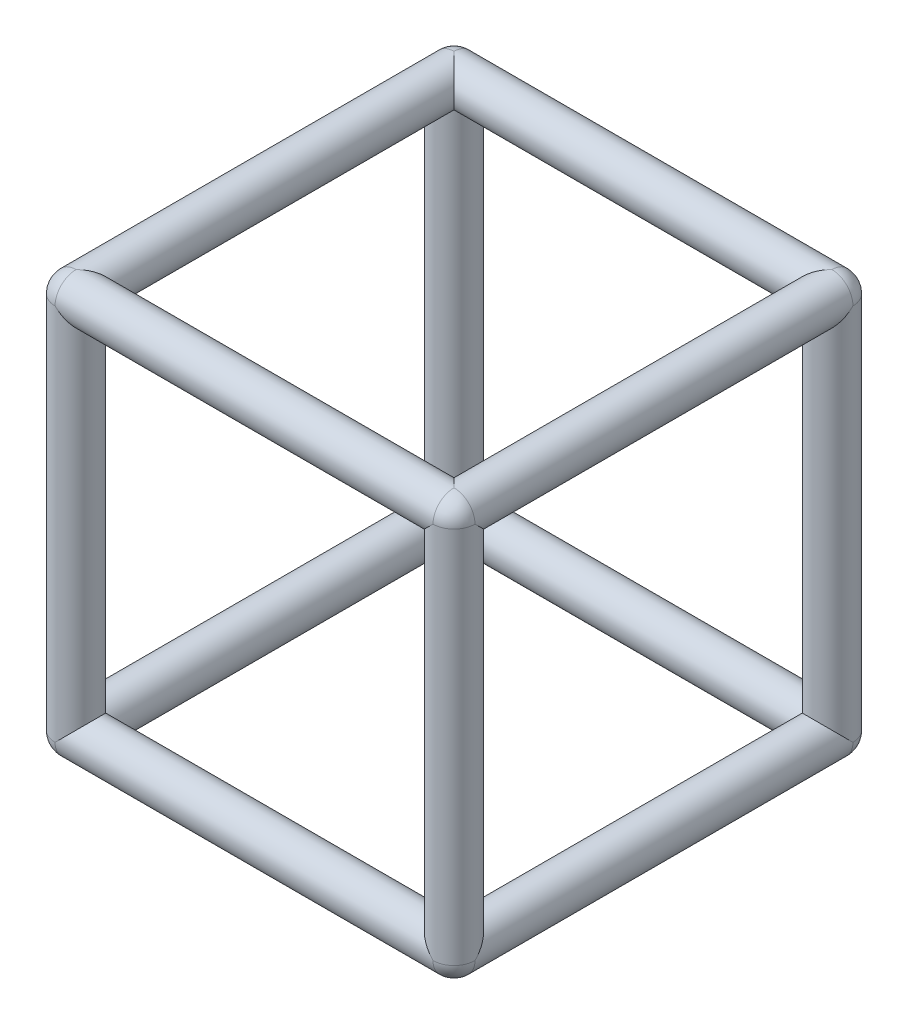
SolidWorks part; units mm, degrees
ref_plane "Front Plane" through (0, 0, 0) normal (0, 0, 1) x (1, 0, 0)
ref_plane "Top Plane" through (0, 0, 0) normal (0, 1, 0) x (1, 0, 0)
ref_plane "Right Plane" through (0, 0, 0) normal (1, 0, 0) x (0, 0, -1)
other "Bounding Box"
ref_plane "Default Plane" through (-139.7, 0, 139.7) normal (0, 0, -1) x (-1, 0, 0)
sketch "Sketch5" plane through (0, 0, 0) normal (0, 1, 0) x (1, 0, 0)
  line L0 (-114.3, 114.3) -> (-63.6437, 114.3) construction
  line L1 (-114.3, 114.3) -> (-114.3, 62.9666) construction
  circle A0 centre (-114.3, 114.3) radius 12.7
  dimension "D1" = 25.4
  dimension "D2" = 114.3
  dimension "D3" = 114.3
extrude "Boss-Extrude2" add sketch "Sketch5" along normal blind 254
fillet "Fillet2" radius 12.7 2 edges at (-114.3, 0, -101.6) (-114.3, 254, -101.6)
pattern_linear "LPattern1" count 2 spacing 228.6 along (1, 0, 0) count 2 spacing 228.6 along (0, 0, 1) of bodies 105
sketch "Sketch6" plane through (0, 0, 0) normal (1, 0, 0) x (0, 0, -1)
  line L0 (-101.6, 241.3) -> (-127, 241.3) construction
  line L1 (-114.3, 241.3) -> (-114.3, 190.0479) construction
  circle A0 centre (-114.3, 241.3) radius 12.7
  arc A1 (-101.6, 241.3) -> (-127, 241.3) centre (-114.3, 241.3) ccw construction
extrude "Boss-Extrude3" add sketch "Sketch6" along normal mid plane 228.6
pattern_linear "LPattern2" count 2 spacing 228.6 along (0, 0, -1) count 2 spacing 228.6 along (0, -1, 0) of "Boss-Extrude3"
sketch "Sketch8" plane through (0, 0, 0) normal (0, 0, 1) x (1, 0, 0)
  line L0 (-114.3, 241.3) -> (-73.6766, 241.3) construction
  line L1 (-114.3, 241.3) -> (-114.3, 198.0194) construction
  circle A0 centre (-114.3, 241.3) radius 12.7
  arc A1 (-114.3, 254) -> (-127, 241.3) centre (-114.3, 241.3) ccw construction
  dimension "D1" = 25.4
extrude "Boss-Extrude4" add sketch "Sketch8" along normal mid plane 228.6
pattern_linear "LPattern3" count 2 spacing 228.6 along (1, 0, 0) count 2 spacing 228.6 along (0, -1, 0) of "Boss-Extrude4"
